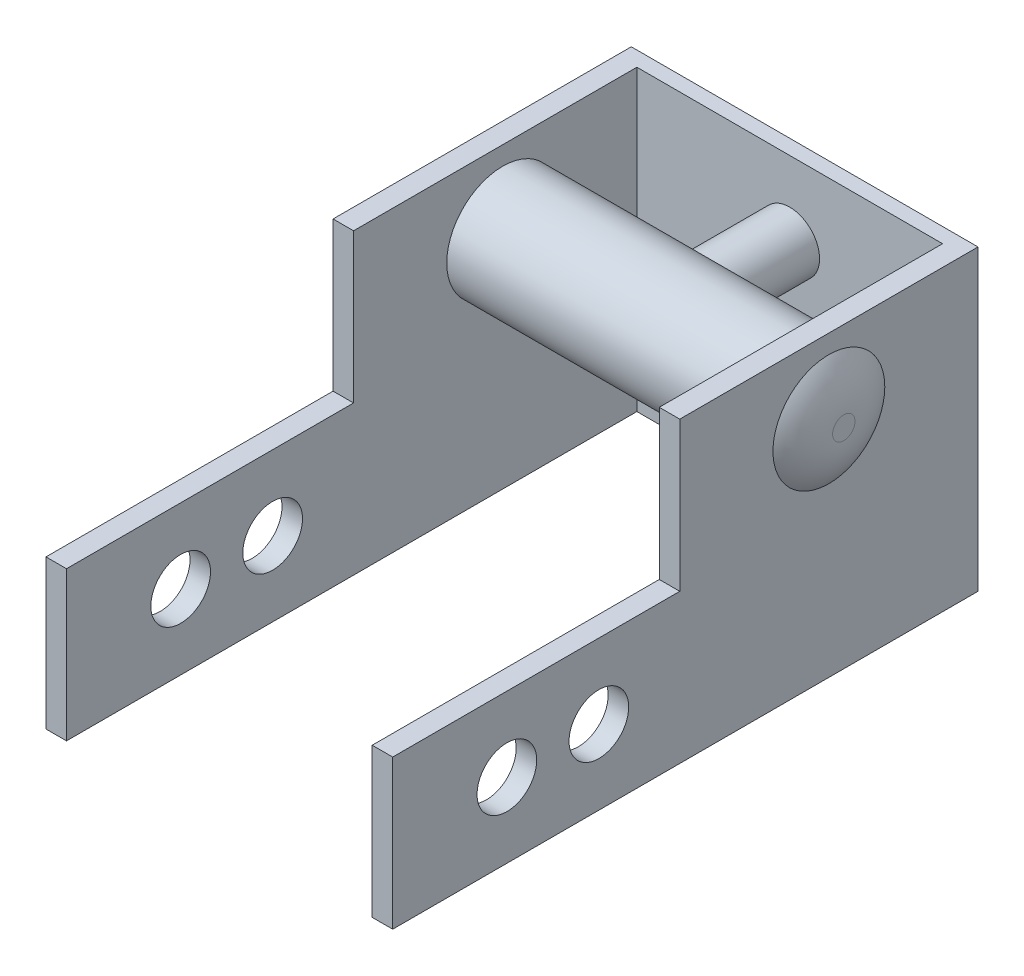
SolidWorks part; units mm, degrees
material "1023 碳钢板 (SS)"
ref_plane "前视基准面" through (0, 0, 0) normal (0, 0, 1) x (1, 0, 0)
ref_plane "上视基准面" through (0, 0, 0) normal (0, 1, 0) x (1, 0, 0)
ref_plane "右视基准面" through (0, 0, 0) normal (1, 0, 0) x (0, 0, -1)
other "Configuration Table"
sketch "草图1" plane through (0, 0, 0) normal (1, 0, 0) x (0, 0, -1)
  line L0 (-18.6744, -9.0019) -> (21.3256, -9.0019)
  line L1 (21.3256, -9.0019) -> (21.3256, 30.9981)
  line L2 (21.3256, 30.9981) -> (-18.6744, 30.9981)
  line L3 (-18.6744, 30.9981) -> (-18.6744, -9.0019)
  dimension "D1" = 40
  dimension "D2" = 40
extrude "凸台-拉伸2" add sketch "草图1" along normal blind 46.5
sketch "草图3" plane through (46.5, 0, 0) normal (1, 0, 0) x (0, 0, -1)
  line L0 (-18.6744, -9.0019) -> (-57.1744, -9.0019)
  line L1 (-57.1744, -9.0019) -> (-57.1744, 10.9981)
  line L2 (-57.1744, 10.9981) -> (-18.6744, 10.9981)
  line L3 (-18.6744, 30.9981) -> (-18.6744, -9.0019) construction
  line L4 (-18.6744, 10.9981) -> (-18.6744, -9.0019)
  dimension "D1" = 38.5
  dimension "D2" = 20
extrude "凸台-拉伸3" add sketch "草图3" against normal blind 2.75
sketch "草图4" plane through (0, 0, 0) normal (-1, 0, 0) x (0, 0, 1)
  line L0 (18.6744, 10.9981) -> (57.1744, 10.9981)
  line L1 (57.1744, 10.9981) -> (57.1744, -9.0019)
  line L2 (57.1744, -9.0019) -> (18.6744, -9.0019)
  line L3 (18.6744, -9.0019) -> (18.6744, 10.9981)
extrude "凸台-拉伸4" add sketch "草图4" against normal blind 2.75
sketch "草图5" plane through (0, 0, 18.6744) normal (0, 0, 1) x (1, 0, 0)
  line L0 (2.75, 10.9981) -> (2.75, 30.9981)
  line L1 (2.75, 30.9981) -> (43.75, 30.9981)
  line L2 (43.75, 30.9981) -> (43.75, 10.9981)
  line L4 (46.5, 30.9981) -> (0, 30.9981) construction
  line L5 (2.75, 10.9981) -> (2.75, -9.0019)
  line L6 (2.75, -9.0019) -> (43.75, -9.0019)
  line L7 (43.75, -9.0019) -> (43.75, 10.9981)
  dimension "D1" = 0
extrude "切除-拉伸1" cut sketch "草图5" against normal blind 38
sketch "草图6" plane through (0, 0, 0) normal (-1, 0, 0) x (0, 0, 1)
  line L0 (-1.3256, 30.9981) -> (-1.3256, -19.6471) construction
  line L1 (-21.3256, 30.9981) -> (18.6744, 30.9981) construction
  line L2 (18.6744, 30.9981) -> (18.6744, 10.9981) construction
  line L3 (18.6744, 20.9981) -> (-26.2182, 20.9981) construction
  circle A0 centre (-1.3256, 20.9981) radius 7.5
  dimension "D1" = 15
extrude "凸台-拉伸5" add sketch "草图6" against normal blind 48.5
sketch "草图7" plane through (48.5, 0, 0) normal (1, 0, 0) x (0, 0, -1)
  circle A0 centre (1.3256, 20.9981) radius 7.5
extrude "凸台-拉伸6" add sketch "草图7" against normal blind 50.5
fillet "圆角1" radius 10 2 edges at (48.5, 20.9981, 6.1744) (-2, 20.9981, -8.8256)
sketch "草图8" plane through (46.5, 0, 0) normal (1, 0, 0) x (0, 0, -1)
  line L0 (-57.1744, 0.9981) -> (26.5012, 0.9981) construction
  line L1 (-57.1744, 10.9981) -> (-57.1744, -9.0019) construction
  circle A0 centre (-41.8633, 0.9981) radius 4
  circle A1 centre (-29.526, 0.9981) radius 4
  dimension "D1" = 8
  dimension "D2" = 8
extrude "切除-拉伸2" cut sketch "草图8" against normal blind 50.5
sketch "草图9" plane through (0, 0, -21.3256) normal (0, 0, -1) x (-1, 0, 0)
  line L0 (-23.25, 30.9981) -> (-23.25, -11.2252) construction
  line L1 (-46.5, 30.9981) -> (0, 30.9981) construction
  line L2 (-48.5, 20.9981) -> (6.3065, 20.9981) construction
  line L3 (-48.5, 22.4981) -> (-48.5, 19.4981) construction
  circle A0 centre (-23.25, 20.9981) radius 6
  dimension "D1" = 12
extrude "凸台-拉伸7" add sketch "草图9" along normal blind 6
sketch "草图10" plane through (0, 0, -27.3256) normal (0, 0, -1) x (-1, 0, 0)
  circle A0 centre (-23.25, 20.9981) radius 4
  dimension "D1" = 8
extrude "凸台-拉伸9" add sketch "草图10" against normal blind 20
cosmetic thread "装饰螺纹线1" parameters "D2"=7
fillet "圆角3" radius 6 1 edges at (17.25, 20.9981, -27.3256)
